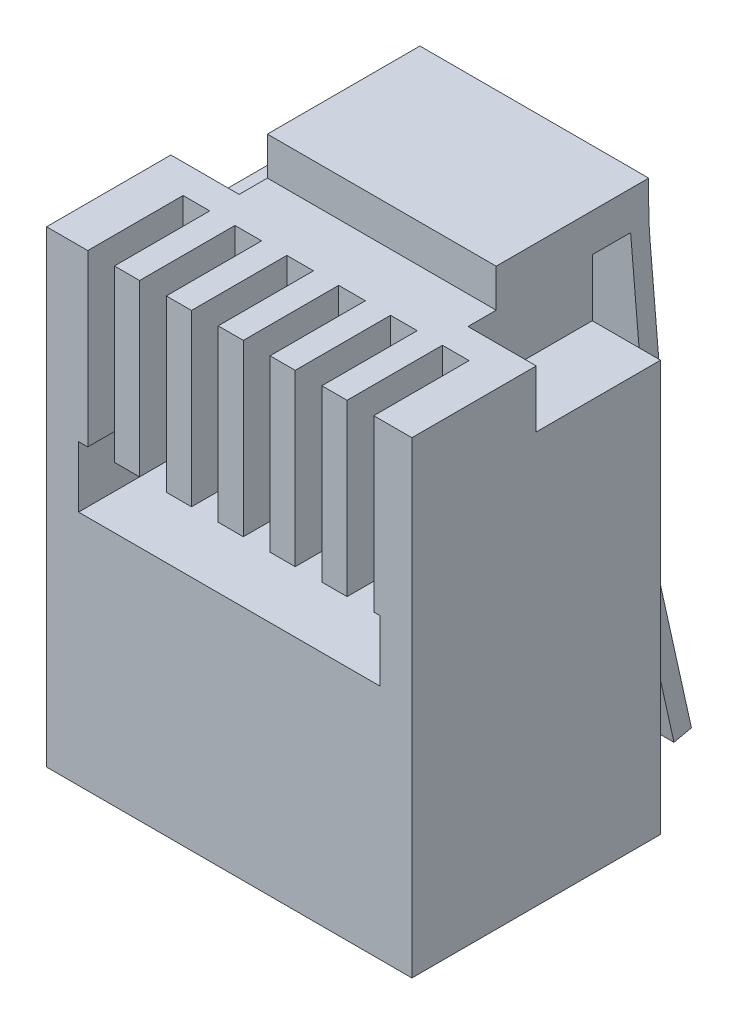
SolidWorks part; units mm, degrees
ref_plane "前视基准面" through (0, 0, 0) normal (0, 0, 1) x (1, 0, 0)
ref_plane "上视基准面" through (0, 0, 0) normal (0, 1, 0) x (1, 0, 0)
ref_plane "右视基准面" through (0, 0, 0) normal (1, 0, 0) x (0, 0, -1)
sketch "草图1" plane through (0, 0, 0) normal (0, 0, 1) x (1, 0, 0)
  line L1 (0, 0) -> (9.58, 0)
  line L2 (0, 0) -> (0, 12.27)
  line L3 (0, 12.27) -> (9.58, 12.27)
  line L4 (9.58, 0) -> (9.58, 12.27)
  dimension "D1" = 9.58
  dimension "D2" = 12.27
extrude "凸台-拉伸1" add sketch "草图1" along normal blind 6.52
sketch "草图2" plane through (0, 0, 6.52) normal (0, 0, 1) x (1, 0, 0)
  line L0 (9.58, 12.27) -> (0, 12.27) construction
  line L1 (0.84, 7.81) -> (8.74, 7.81)
  line L2 (0.84, 7.81) -> (0.84, 6.21)
  line L3 (0.84, 6.21) -> (8.74, 6.21)
  line L4 (8.74, 7.81) -> (8.74, 6.21)
  line L5 (4.79, 12.27) -> (4.79, 3.1744) construction
  point P7 (4.79, 7.81)
  dimension "D1" = 1.6
  dimension "D2" = 7.9
  dimension "D3" = 4.46
extrude "切除-拉伸1" cut sketch "草图2" against normal blind 4
sketch "草图3" plane through (0, 0, 6.52) normal (0, 0, 1) x (1, 0, 0)
  line L0 (9.58, 0) -> (9.58, 12.27) construction
  line L1 (7.88, 12.5426) -> (8.58, 12.5426)
  line L2 (7.88, 12.5426) -> (7.88, 7.4745)
  line L3 (7.88, 7.4745) -> (8.58, 7.4745)
  line L4 (8.58, 12.5426) -> (8.58, 7.4745)
  line L5 (6.52, 12.5426) -> (6.52, 7.4745)
  line L6 (7.22, 12.5426) -> (7.22, 7.4745)
  line L7 (6.52, 12.5426) -> (7.22, 12.5426)
  line L8 (6.52, 7.4745) -> (7.22, 7.4745)
  line L9 (5.16, 12.5426) -> (5.16, 7.4745)
  line L10 (5.86, 12.5426) -> (5.86, 7.4745)
  line L11 (5.16, 12.5426) -> (5.86, 12.5426)
  line L12 (5.16, 7.4745) -> (5.86, 7.4745)
  line L13 (3.8, 12.5426) -> (3.8, 7.4745)
  line L14 (4.5, 12.5426) -> (4.5, 7.4745)
  line L15 (3.8, 12.5426) -> (4.5, 12.5426)
  line L16 (3.8, 7.4745) -> (4.5, 7.4745)
  line L17 (2.44, 12.5426) -> (2.44, 7.4745)
  line L18 (3.14, 12.5426) -> (3.14, 7.4745)
  line L19 (2.44, 12.5426) -> (3.14, 12.5426)
  line L20 (2.44, 7.4745) -> (3.14, 7.4745)
  line L21 (1.08, 12.5426) -> (1.08, 7.4745)
  line L22 (1.78, 12.5426) -> (1.78, 7.4745)
  line L23 (1.08, 12.5426) -> (1.78, 12.5426)
  line L24 (1.08, 7.4745) -> (1.78, 7.4745)
  dimension "D1" = 0.7
  dimension "D2" = 1
  dimension "D3" = 6
extrude "切除-拉伸2" cut sketch "草图3" against normal blind 2.5
sketch "草图4" plane through (0, 12.27, 0) normal (0, 1, 0) x (1, 0, 0)
  line L0 (1.08, -6.52) -> (0, -6.52) construction
  line L1 (1.79, 1.48) -> (7.79, 1.48)
  line L2 (1.79, 1.48) -> (1.79, -2.52)
  line L3 (1.79, -2.52) -> (7.79, -2.52)
  line L4 (7.79, 1.48) -> (7.79, -2.52)
  line L5 (4.79, 1.9791) -> (4.79, -9.6555) construction
  line L6 (9.58, 0) -> (0, 0) construction
  point P6 (4.79, 1.48)
  point P11 (4.79, 0)
  dimension "D1" = 6
  dimension "D2" = 4
  dimension "D3" = 4
extrude "凸台-拉伸2" add sketch "草图4" along normal blind 1
sketch "草图5" plane through (0, 12.27, 0) normal (0, 1, 0) x (1, 0, 0)
  line L0 (7.79, -2.52) -> (7.79, 1.48) construction
  line L1 (7.79, 0.5118) -> (9.58, 0.5118)
  line L2 (7.79, 0.5118) -> (7.79, -3.26)
  line L3 (7.79, -3.26) -> (9.58, -3.26)
  line L4 (9.58, 0.5118) -> (9.58, -3.26)
  line L5 (9.58, -6.52) -> (9.58, 0) construction
  line L6 (4.79, 3.8147) -> (4.79, -8.6817) construction
  line L7 (7.79, 1.48) -> (1.79, 1.48) construction
  line L8 (0, 0.5118) -> (0, -3.26)
  line L9 (1.79, -3.26) -> (0, -3.26)
  line L10 (1.79, 0.5118) -> (1.79, -3.26)
  line L11 (1.79, 0.5118) -> (0, 0.5118)
  point P12 (4.79, 1.48)
extrude "切除-拉伸3" cut sketch "草图5" against normal blind 1.5
ref_plane "基准面1" through (4.79, 0, 0) normal (-1, 0, 0) x (0, 0, 1)
sketch "草图6" plane through (4.79, 0, 0) normal (-1, 0, 0) x (0, 0, 1)
  line L0 (-1.48, 12.27) -> (-1.75, 8.9426)
  line L1 (-1.75, 8.9426) -> (-1.2781, 8.9043)
  line L2 (-1.2781, 8.9043) -> (-1.005, 12.27)
  line L3 (-1.48, 12.27) -> (-1.005, 12.27)
  line L4 (0, 0) -> (0, 10.77) construction
  dimension "D1" = 1.75
extrude "凸台-拉伸3" add sketch "草图6" along normal mid plane 6
sketch "草图7" plane through (4.79, 0, 0) normal (-1, 0, 0) x (0, 0, 1)
  line L0 (-1.75, 8.9426) -> (-4, -1.1736)
  line L1 (-4, -1.1736) -> (-3.5423, -1.2755)
  line L2 (-3.5423, -1.2755) -> (-1.2781, 8.9043)
  line L3 (-1.2781, 8.9043) -> (-1.75, 8.9426)
  line L4 (0, 0) -> (0, 10.77) construction
  dimension "D1" = 4
extrude "凸台-拉伸4" add sketch "草图7" along normal mid plane 3.2
fillet "圆角1" radius 10 1 edges at (4.79, 12.27, -1.48)
sketch "草图8" plane through (0, 0, 0) normal (0, -1, 0) x (1, 0, 0)
  line L0 (0, 6.52) -> (0, 0) construction
  line L1 (1, 5.52) -> (8.58, 5.52)
  line L2 (1, 5.52) -> (1, 1)
  line L3 (1, 1) -> (8.58, 1)
  line L4 (8.58, 5.52) -> (8.58, 1)
  line L5 (0, 0) -> (9.58, 0) construction
  line L6 (9.58, 6.52) -> (9.58, 0) construction
  line L7 (0, 6.52) -> (9.58, 6.52) construction
  dimension "D1" = 1
  dimension "D2" = 1
  dimension "D3" = 1
  dimension "D4" = 1
extrude "切除-拉伸4" cut sketch "草图8" against normal blind 6
sketch "草图9" plane through (0, 6, 0) normal (0, -1, 0) x (1, 0, 0)
  line L0 (4.79, 2.4011) -> (4.79, -2.4011) construction
  point P0 (4.79, 3.26)
